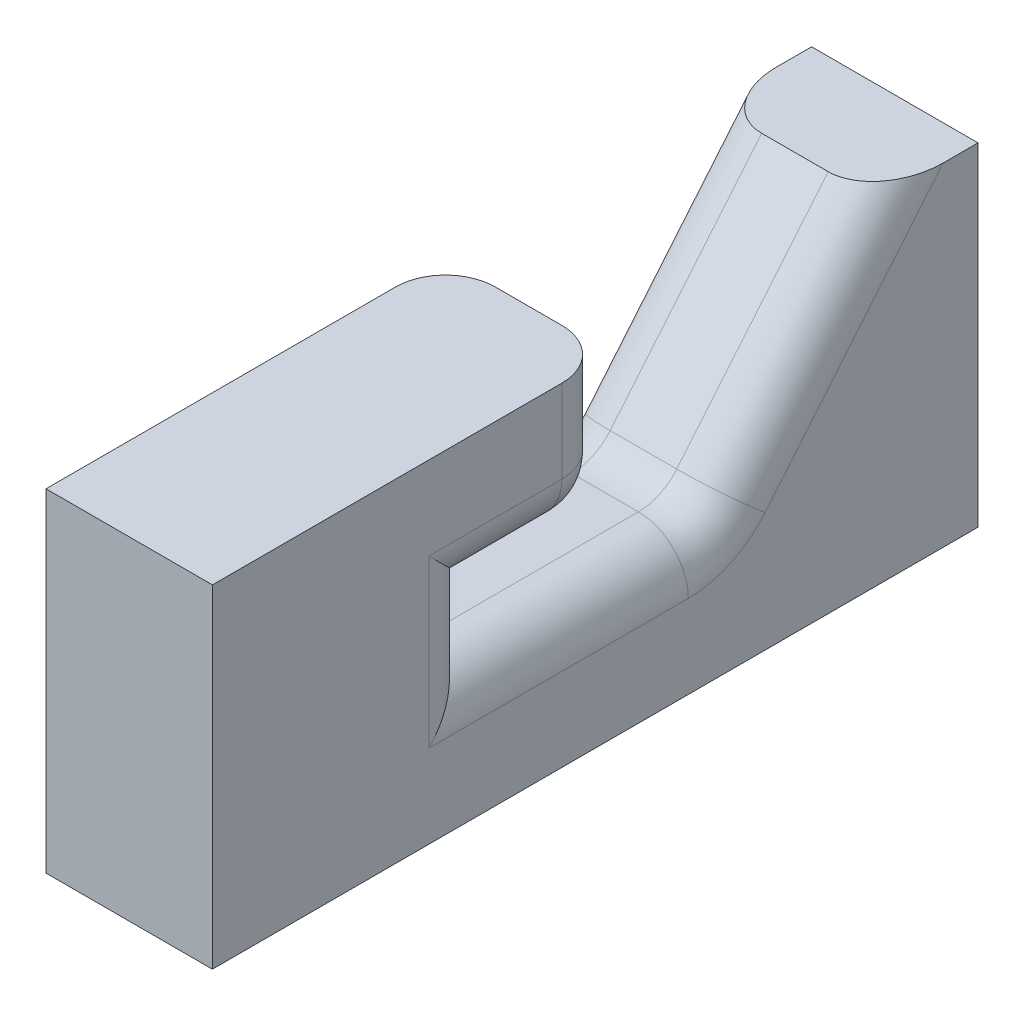
SolidWorks part; units mm, degrees
ref_plane "Front Plane" through (0, 0, 0) normal (1, 0, 0) x (0, 1, 0)
ref_plane "Top Plane" through (0, 0, 0) normal (0, 0, 1) x (0, 1, 0)
ref_plane "Right Plane" through (0, 0, 0) normal (0, 1, 0) x (-1, 0, 0)
sketch "Sketch2" plane through (0, 0, 0) normal (1, 0, 0) x (0, 1, 0)
  line L1 (0, 0) -> (10, 0)
  line L2 (0, 0) -> (0, 23)
  line L3 (0, 23) -> (10, 23)
  line L4 (10, 0) -> (10, 23)
  dimension "D1" = 23
  dimension "D2" = 10
extrude "Boss-Extrude1" add sketch "Sketch2" along normal blind 5
sketch "Sketch3" plane through (5, 0, 0) normal (1, 0, 0) x (0, 1, 0)
  line L0 (4, 11) -> (4, 8)
  line L1 (10, 23) -> (6, 23)
  line L2 (10, 23) -> (10, 11)
  line L3 (10, 11) -> (6, 11)
  line L4 (6, 23) -> (6, 11)
  line L5 (6, 11) -> (4, 11)
  line L6 (6, 11) -> (6, 15)
  line L7 (6, 15) -> (4, 15)
  line L8 (4, 11) -> (4, 15)
  line L10 (4, 8) -> (10, 3)
  line L11 (10, 0) -> (10, 23) construction
  line L12 (0, 0) -> (10, 0) construction
  line L13 (10, 3) -> (10, 11)
  line M12 (10, 0) -> (10, 23)
  dimension "D1" = 12
  dimension "D2" = 4
  dimension "D3" = 2
  dimension "D4" = 4
  dimension "D5" = 3
  dimension "D6" = 3
extrude "Cut-Extrude1" cut sketch "Sketch3" against normal through all contours L8 L5 L4 L7 | L0 L10 L3 L5 M12 region at (5, 7.4545, 8.0606) region at (5, 5, 13)
fillet "Fillet2" radius 1.5 12 edges at (2.5, 6, 11) (5, 6, 13) (5, 4, 11.5) (5, 5, 15) (0, 4, 11.5) (0, 5, 15) (0, 6, 13) (0, 7, 5.5) (5, 7, 5.5) (2.5, 4, 8) (0, 8, 11) (5, 8, 11)
equation "\"whitekey_cutout_length\"= 101.5"
equation "\"mount_recess_length\"=50"
equation "\"mount_recess_height\"=12.5"
equation "\"mount_recess_depth\"=1.5"
equation "\"wall_thickness\"=8"
equation "\"base_mount_height\"=35"
equation "\"base_rear_length\"=80"
equation "\"D1@Sketch2\"=\"base_mount_height\"-11-1"
